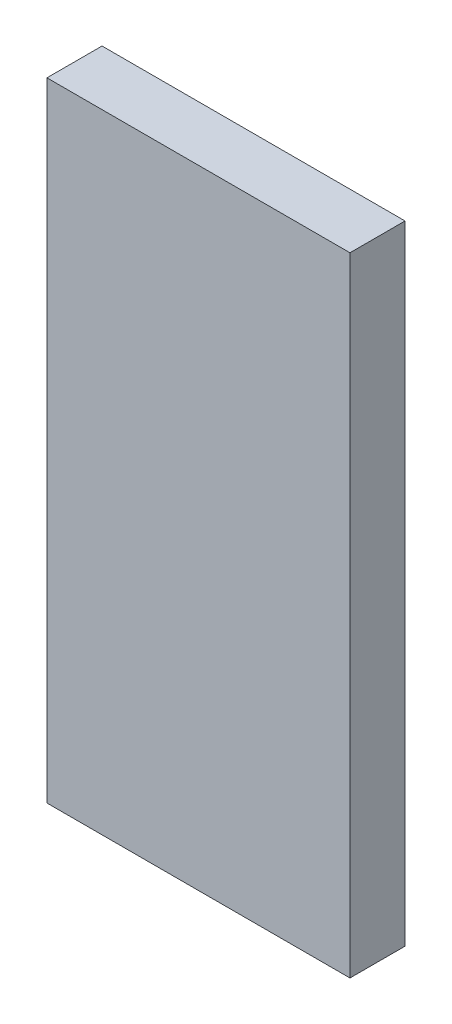
SolidWorks part; units mm, degrees
ref_plane "Front Plane" through (0, 0, 0) normal (0, 0, 1) x (1, 0, 0)
ref_plane "Top Plane" through (0, 0, 0) normal (0, 1, 0) x (1, 0, 0)
ref_plane "Right Plane" through (0, 0, 0) normal (1, 0, 0) x (0, 0, -1)
sketch "Sketch1" plane through (0, 0, 0) normal (0, 1, 0) x (1, 0, 0)
  line L1 (-19.5, 77.5) -> (19.5, 77.5)
  line L2 (-19.5, 77.5) -> (-19.5, -77.5)
  line L3 (-19.5, -77.5) -> (19.5, -77.5)
  line L4 (19.5, 77.5) -> (19.5, -77.5)
  line L5 (-19.5, 77.5) -> (19.5, -77.5) construction
  line L6 (-19.5, -77.5) -> (19.5, 77.5) construction
  point P0 (0, 0)
  dimension "D1" = 39
  dimension "D2" = 155
extrude "Boss-Extrude1" add sketch "Sketch1" along normal blind 2
sketch "Sketch2" plane through (0, 2, 0) normal (0, 1, 0) x (1, 0, 0)
  line L0 (-17.5, -75.5) -> (-17.5, -77.5)
  line L1 (-19.5, 77.5) -> (19.5, 77.5)
  line L2 (-19.5, 77.5) -> (-19.5, -77.5)
  line L3 (-19.5, -77.5) -> (19.5, -77.5)
  line L4 (19.5, 77.5) -> (19.5, -77.5)
  line L5 (-17.5, 75.5) -> (17.5, 75.5)
  line L6 (-17.5, 75.5) -> (-17.5, -75.5)
  line L7 (-17.5, -75.5) -> (17.5, -75.5)
  line L8 (17.5, 75.5) -> (17.5, -75.5)
  line L9 (-17.5, 75.5) -> (17.5, -75.5) construction
  line L10 (-17.5, -75.5) -> (17.5, 75.5) construction
  line L11 (17.5, -75.5) -> (17.5, -77.5)
  point P6 (0, 0)
  line M9 (19.5, -77.5) -> (19.5, 77.5)
  line M10 (19.5, 77.5) -> (-19.5, 77.5)
  line M11 (-19.5, 77.5) -> (-19.5, -77.5)
  line M12 (-19.5, -77.5) -> (19.5, -77.5)
  dimension "D1" = 2
  dimension "D2" = 2
extrude "Boss-Extrude2" add sketch "Sketch2" along normal blind 38 contours L8 L11 L3 L0 L6 L5 M9 M10 M11 M12 region at (-19.0983, 2, 76.5)
sketch "Sketch3" plane through (0, 2, 0) normal (0, 1, 0) x (1, 0, 0)
  line L0 (-17.5, 75.5) -> (-17.5, -77.5) construction
  line L1 (-17.5, -77.5) -> (-15.5, -77.5)
  line L2 (-17.5, -77.5) -> (-17.5, -75.5)
  line L3 (-17.5, -75.5) -> (-15.5, -75.5)
  line L4 (-15.5, -77.5) -> (-15.5, -75.5)
  line L5 (-17.5, -73.3) -> (-15.5, -73.3)
  line L6 (-17.5, -73.3) -> (-17.5, -71.3)
  line L7 (-17.5, -71.3) -> (-15.5, -71.3)
  line L8 (-15.5, -73.3) -> (-15.5, -71.3)
  line L9 (17.5, 75.5) -> (17.5, -77.5) construction
  line L10 (17.5, -77.5) -> (15.5, -77.5)
  line L11 (17.5, -77.5) -> (17.5, -75.5)
  line L12 (17.5, -75.5) -> (15.5, -75.5)
  line L13 (15.5, -77.5) -> (15.5, -75.5)
  line L14 (17.5, -73.3) -> (15.5, -73.3)
  line L15 (17.5, -73.3) -> (17.5, -71.3)
  line L16 (17.5, -71.3) -> (15.5, -71.3)
  line L17 (15.5, -73.3) -> (15.5, -71.3)
  line L18 (15.5, -75.5) -> (15.5, -73.3) construction
  line L19 (-15.5, -73.3) -> (15.5, -73.3) construction
  line L20 (-15.5, -75.5) -> (-15.5, -73.3) construction
  line L21 (-15.5, -75.5) -> (15.5, -75.5) construction
  line L22 (15.5, -71.3) -> (-15.5, -71.3) construction
  dimension "D1" = 2
  dimension "D2" = 2
  dimension "D3" = 2.2
  dimension "D4" = 2
extrude "Boss-Extrude3" add sketch "Sketch3" along normal up to surface (38 mm away) up to face at (0, 40, 0.5)
sketch "Sketch4" plane through (0, 0, -75.5) normal (0, 0, 1) x (1, 0, 0)
  line L0 (-17.5, 40) -> (-15.5, 40)
  line L1 (-17.5, 40) -> (17.5, 40) construction
  line L2 (-15.5, 40) -> (-15.5, 38)
  line L3 (-15.5, 38) -> (-17.5, 38)
  line L5 (-17.5, 38) -> (-17.5, 40)
  line L7 (-17.5, 40) -> (-17.5, 2) construction
  line L8 (-15.5, 33.8) -> (-17.5, 31.8)
  line L9 (-17.5, 31.8) -> (-17.5, 35.8)
  line L10 (-15.5, 33.8) -> (-15.5, 35.8)
  line L11 (-15.5, 35.8) -> (-17.5, 35.8)
  line L12 (0, 0) -> (0, 40) construction
  line L13 (15.5, 35.8) -> (17.5, 35.8)
  line L14 (15.5, 33.8) -> (15.5, 35.8)
  line L15 (17.5, 31.8) -> (17.5, 35.8)
  line L16 (15.5, 33.8) -> (17.5, 31.8)
  line L17 (17.5, 38) -> (17.5, 40)
  line L18 (15.5, 38) -> (17.5, 38)
  line L19 (15.5, 40) -> (15.5, 38)
  line L20 (17.5, 40) -> (15.5, 40)
  dimension "D1" = 2
  dimension "D2" = 2
  dimension "D3" = 45
  dimension "D4" = 2.2
  dimension "D5" = 2
extrude "Boss-Extrude4" add sketch "Sketch4" along normal up to surface (153 mm away)
sketch "Sketch5" plane through (0, 2, 0) normal (0, 1, 0) x (1, 0, 0)
  line L1 (-15.5, -77.5) -> (15.5, -77.5)
  line L2 (-15.5, -77.5) -> (-15.5, -75.5)
  line L3 (-15.5, -75.5) -> (15.5, -75.5)
  line L4 (15.5, -77.5) -> (15.5, -75.5)
  line L5 (-15.5, -71.3) -> (15.5, -71.3)
  line L6 (-15.5, -71.3) -> (-15.5, -73.3)
  line L7 (-15.5, -73.3) -> (15.5, -73.3)
  line L8 (15.5, -71.3) -> (15.5, -73.3)
sketch "Sketch6" plane through (0, 0, -75.5) normal (0, 0, 1) x (1, 0, 0)
  line L0 (-17.5, 38) -> (-15.5, 38) construction
  line L1 (-17.5, 38) -> (17.5, 38)
  line L2 (-17.5, 38) -> (-17.5, 35.8)
  line L3 (-17.5, 35.8) -> (17.5, 35.8)
  line L4 (17.5, 38) -> (17.5, 35.8)
  line L5 (-17.5, 38) -> (-17.5, 35.8) construction
  line L6 (-15.5, 35.8) -> (-17.5, 35.8) construction
extrude "Cut-Extrude1" cut sketch "Sketch6" along normal through all
sketch "Sketch7" plane through (0, 2, 0) normal (0, 1, 0) x (1, 0, 0)
  line L1 (-17.5, -75.5) -> (17.5, -75.5)
  line L2 (-17.5, -75.5) -> (-17.5, -73.3)
  line L3 (-17.5, -73.3) -> (17.5, -73.3)
  line L4 (17.5, -75.5) -> (17.5, -73.3)
extrude "Cut-Extrude2" cut sketch "Sketch7" along normal through all
extrude "Boss-Extrude5" add sketch "Sketch5" along normal blind 2
sketch "Sketch8" plane through (0, 0, 0) normal (1, 0, 0) x (0, 0, -1)
  line L0 (75.5, 40) -> (73.5, 40)
  line L1 (-73.3, 40) -> (75.5, 40) construction
  line L2 (73.5, 40) -> (73.5, 38)
  line L3 (-73.3, 38) -> (75.5, 38) construction
  line L4 (73.5, 38) -> (75.5, 38)
  line L5 (75.5, 38) -> (75.5, 40)
  line L6 (75.5, 35.8) -> (73.5, 35.8)
  line L7 (-73.3, 35.8) -> (75.5, 35.8) construction
  line L8 (73.5, 35.8) -> (73.5, 33.8)
  line L9 (-71.3, 33.8) -> (75.5, 33.8) construction
  line L10 (73.5, 33.8) -> (75.5, 31.8)
  line L11 (75.5, 31.8) -> (75.5, 35.8)
  dimension "D1" = 2
extrude "Boss-Extrude6" add sketch "Sketch8" along normal up to surface and the other way up to surface up to face at (17.5, 16.9, -2.1) other way up to face at (-17.5, 16.9, -2.1)
sketch "Sketch10" plane through (-17.5, 0, 0) normal (1, 0, 0) x (0, 0, -1)
  line L1 (-75.5, 35.8) -> (-77.5, 35.8)
  line L2 (-75.5, 35.8) -> (-75.5, 38)
  line L3 (-75.5, 38) -> (-77.5, 38)
  line L4 (-77.5, 35.8) -> (-77.5, 38)
  line L5 (-73.3, 40) -> (-75.5, 40)
  line L6 (-73.3, 40) -> (-73.3, 38)
  line L7 (-73.3, 38) -> (-75.5, 38)
  line L8 (-75.5, 40) -> (-75.5, 38)
  line M1 (-75.5, 40) -> (-75.5, 38)
  line M2 (-75.5, 38) -> (-77.5, 38)
  line M3 (-77.5, 38) -> (-77.5, 35.8)
  line M4 (-77.5, 35.8) -> (-75.5, 35.8)
  line M11 (-73.3, 38) -> (-73.3, 40)
  line M12 (-73.3, 40) -> (-75.5, 40)
extrude "Boss-Extrude8" add sketch "Sketch10" along normal up to surface (2 mm away) contours L2 M4 M2 M3 | L7 M11 M12 M1 region at (-17.5, 39, 74.4) region at (-17.5, 36.9, 76.5) up to face at (-15.5, 39, -0.1)
sketch "Sketch11" plane through (17.5, 0, 0) normal (-1, 0, 0) x (0, 0, 1)
  line L1 (75.5, 35.8) -> (77.5, 35.8)
  line L2 (75.5, 35.8) -> (75.5, 38)
  line L3 (75.5, 38) -> (77.5, 38)
  line L4 (77.5, 35.8) -> (77.5, 38)
  line L5 (73.3, 40) -> (75.5, 40)
  line L6 (73.3, 40) -> (73.3, 38)
  line L7 (73.3, 38) -> (75.5, 38)
  line L8 (75.5, 40) -> (75.5, 38)
  line M2 (75.5, 35.8) -> (77.5, 35.8)
  line M3 (77.5, 35.8) -> (77.5, 38)
  line M4 (77.5, 38) -> (75.5, 38)
  line M5 (75.5, 38) -> (75.5, 40)
  line M6 (75.5, 40) -> (73.3, 40)
  line M7 (73.3, 40) -> (73.3, 38)
extrude "Boss-Extrude9" add sketch "Sketch11" along normal up to surface (2 mm away) contours L2 M2 M3 M4 | L7 M7 M5 M6 region at (17.5, 36.9, 76.5) region at (17.5, 39, 74.4) up to face at (15.5, 39, -0.1)
fillet "Fillet2" radius 2.5 17 edges at (-17.5, 16.9, 71.3) (17.5, 16.9, 71.3) (19.5, 20, 77.5) (-19.5, 20, 77.5) (-19.5, 20, -77.5) (-17.5, 16.9, -75.5) (17.5, 16.9, -75.5) (19.5, 20, -77.5) (-19.5, 40, 0) (0, 40, -77.5) (19.5, 40, 0) (0, 0, -77.5) (0, 0, 77.5) (-19.5, 0, 0) (19.5, 0, 0) (-17.5, 40, 77.5) (17.5, 40, 77.5)
sketch "Sketch13" plane through (0, 0, -77.5) normal (0, 0, -1) x (-1, 0, 0)
  line L0 (15.5, 37.5) -> (15.5, 4) construction
  line L1 (-15.5, 7) -> (15.5, 7)
  line L2 (-15.5, 7) -> (-15.5, 4)
  line L3 (-15.5, 4) -> (15.5, 4)
  line L4 (15.5, 7) -> (15.5, 4)
  dimension "D1" = 3
sketch "Sketch14" plane through (0, 0, -75.5) normal (0, 0, 1) x (1, 0, 0)
  line L1 (-18.25, 9) -> (18.25, 9)
  line L2 (-18.25, 9) -> (-18.25, 1.25)
  line L3 (-18.25, 1.25) -> (18.25, 1.25)
  line L4 (18.25, 9) -> (18.25, 1.25)
  line L5 (15.5, 7) -> (-15.5, 7) construction
  line L7 (17, 0) -> (17, 2.5) construction
  line L8 (19.5, 2.5) -> (17, 2.5) construction
  line L10 (-19.5, 2.5) -> (-17, 2.5) construction
  point P20 (17, 1.25)
  point P23 (18.25, 2.5)
  point P26 (-18.25, 2.5)
  dimension "D1" = 2
extrude "Boss-Extrude10" add sketch "Sketch14" along normal blind 2
extrude "Cut-Extrude4" cut sketch "Sketch13" against normal blind 2
fillet "Fillet3" radius 2 1 edges at (0, 9, -73.5)
fillet "Fillet4" radius 0.5 12 edges at (0, 4, -77.5) (0, 7, -77.5) (15.5, 7, -76.5) (15.5, 4, -76.5) (15.5, 5.5, -77.5) (-15.5, 4, -76.5) (-15.5, 7, -76.5) (-15.5, 5.5, -77.5) (0, 7, -75.5) (-15.5, 5.5, -75.5) (0, 4, -75.5) (15.5, 5.5, -75.5)
sketch "Sketch15" plane through (0, 0, 0) normal (0, -1, 0) x (1, 0, 0)
  line L0 (0, 77.5) -> (0, 0) construction
  line L1 (-17, 77.5) -> (17, 77.5) construction
  line L2 (0, 0) -> (0, -77.5) construction
  line L4 (17, -77.5) -> (-17, -77.5) construction
  circle A0 centre (0, 38.75) radius 5.1
  circle A1 centre (0, -38.75) radius 5.1
  dimension "D1" = 10.2
extrude "Cut-Extrude5" cut sketch "Sketch15" against normal through all
sketch "Sketch16" plane through (0, 2, 0) normal (0, 1, 0) x (1, 0, 0)
  circle A0 centre (0, 38.75) radius 7.1
  circle A1 centre (0, -38.75) radius 7.1
  circle A2 centre (0, 38.75) radius 5.1 construction
  dimension "D1" = 2
extrude "Boss-Extrude11" add sketch "Sketch16" along normal blind 1
fillet "Fillet5" radius 0.5 4 edges at (0, 2, 45.85) (0, 2, -31.65) (0, 3, 45.85) (0, 3, -31.65)
fillet "Fillet7" radius 0.5 8 edges at (15.5, 40, 0.75) (15.5, 39.2678, 76.7678) (-15.5, 40, 0.75) (-15.5, 39.2678, 76.7678) (0, 40, -73.5) (15.5, 20.75, 77.5) (-15.5, 20.75, 77.5) (0, 4, 77.5)
sketch "Sketch17" plane through (0, 0, 0) normal (0, -1, 0) x (1, 0, 0)
  line L0 (-17, -77.5) -> (-17, 70.3)
  line L1 (-17, -77.5) -> (17, -77.5)
  line L2 (17, -77.5) -> (17, 70.3)
  line L3 (17, -75) -> (17, 75) construction
  line L5 (17, 70.3) -> (15, 71.3)
  line L6 (15, 71.3) -> (15, 77.5)
  line L7 (15, 77.5) -> (-15, 77.5)
  line L8 (-15, 77.5) -> (-15, 71.3)
  line L9 (-15, 71.3) -> (-17, 70.3)
  line L10 (-17, 75) -> (-17, -75) construction
  line L12 (-15, 71.3) -> (15, 71.3) construction
  line L13 (17, 70.3) -> (-17, 70.3) construction
  line L14 (0, 71.3) -> (0, 77.5) construction
  line L15 (-17, 77.5) -> (17, 77.5) construction
  arc A0 (-19.5, -75) -> (-17, -77.5) centre (-17, -75) ccw construction
  dimension "D1" = 1
  dimension "D2" = 30
  dimension "D3" = 6.2
extrude "Cut-Extrude6" cut sketch "Sketch17" against normal blind 6
sketch "Sketch18" plane through (0, 0, 0) normal (0, 0, 1) x (1, 0, 0)
  line L0 (15, 9) -> (-15, 9) construction
  line L1 (-14.5, 9) -> (14.5, 9)
  line L2 (-14.5, 9) -> (-14.5, 6)
  line L3 (-14.5, 6) -> (14.5, 6)
  line L4 (14.5, 9) -> (14.5, 6)
  line L5 (-17, 6) -> (17, 6) construction
  line L6 (0, 6) -> (0, 0) construction
  dimension "D1" = 29
extrude "Cut-Extrude8" cut sketch "Sketch18" against normal through all
sketch "Sketch20" plane through (0, 0, 0) normal (0, 0, 1) x (1, 0, 0)
  line L0 (-16, 40) -> (16, 40) construction
  line L1 (-19.5, 40) -> (-14.5, 40)
  line L2 (-19.5, 40) -> (-19.5, 0)
  line L3 (-19.5, 0) -> (-14.5, 0)
  line L4 (-14.5, 40) -> (-14.5, 0)
  line L5 (-14.5, 6) -> (14.5, 6)
  line L6 (-14.5, 6) -> (-14.5, 40)
  line L7 (-14.5, 40) -> (14.5, 40)
  line L8 (14.5, 6) -> (14.5, 40)
  line L9 (14.5, 40) -> (19.5, 40)
  line L10 (14.5, 40) -> (14.5, 0)
  line L11 (14.5, 0) -> (19.5, 0)
  line L12 (19.5, 40) -> (19.5, 0)
  line L13 (-15, 0) -> (-17, 0) construction
  line L14 (-19.5, 2.5) -> (-19.5, 37.5) construction
  line L15 (17, 0) -> (15, 0) construction
  line L16 (19.5, 37.5) -> (19.5, 2.5) construction
extrude "Cut-Extrude11" cut sketch "Sketch20" against normal through all both and the other way through all contours L12 L9 L8 L10 L11 | L1 L2 L3 L4 region at (17, 20, 0)
sketch "Sketch21" plane through (0, 0, 0) normal (0, 0, 1) x (1, 0, 0)
  line L0 (14.5, 40) -> (-14.5, 40) construction
  line L1 (-14.5, 9) -> (14.5, 9)
  line L2 (-14.5, 9) -> (-14.5, 40)
  line L3 (-14.5, 40) -> (14.5, 40)
  line L4 (14.5, 9) -> (14.5, 40)
  line L5 (-14.5, 9) -> (14.5, 40) construction
  line L6 (-14.5, 40) -> (14.5, 9) construction
  line L8 (-5.5, 9) -> (5.5, 9)
  line L9 (-5.5, 9) -> (-5.5, 40)
  line L10 (-5.5, 40) -> (5.5, 40)
  line L11 (5.5, 9) -> (5.5, 40)
  line L12 (-5.5, 9) -> (5.5, 40) construction
  line L13 (-5.5, 40) -> (5.5, 9) construction
  point P0 (0, 24.5)
  point P7 (0, 24.5)
  dimension "D1" = 11
extrude "Cut-Extrude12" cut sketch "Sketch21" against normal through all contours L1 L9 L3 L2 | L11 L1 L4 L3 region at (-10, 24.5, 0) region at (10, 24.5, 0)
sketch "Sketch22" plane through (0, 0, -75.5) normal (0, 0, 1) x (1, 0, 0)
  line L1 (-5.5, 40) -> (5.5, 40)
  line L2 (-5.5, 40) -> (-5.5, 31.8)
  line L3 (-5.5, 31.8) -> (5.5, 31.8)
  line L4 (5.5, 40) -> (5.5, 31.8)
  line L5 (-5.5, 9) -> (5.5, 9)
  line L6 (-5.5, 9) -> (-5.5, 31.8)
  line L7 (-5.5, 31.8) -> (5.5, 31.8)
  line L8 (5.5, 9) -> (5.5, 31.8)
  line M1 (5.5, 31.8) -> (-5.5, 31.8)
extrude "Cut-Extrude13" cut sketch "Sketch22" against normal through all both and the other way through all contours L4 L1 L2 M1 region at (0, 35.9, -75.5)
